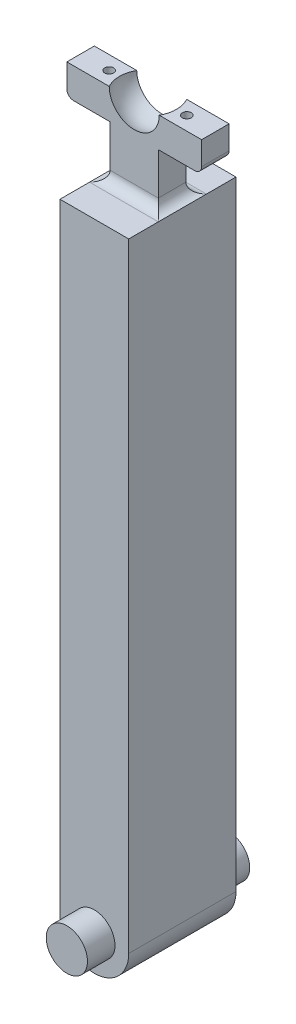
SolidWorks part; units mm, degrees
ref_plane "前视基准面" through (0, 0, 0) normal (0, 0, 1) x (1, 0, 0)
ref_plane "上视基准面" through (0, 0, 0) normal (0, 1, 0) x (1, 0, 0)
ref_plane "右视基准面" through (0, 0, 0) normal (1, 0, 0) x (0, 0, -1)
other "Configuration Table"
sketch "草图1" plane through (0, 0, 0) normal (0, 0, 1) x (1, 0, 0)
  line L0 (-5, 0) -> (5, 0)
  line L1 (5, 0) -> (5, 90)
  line L2 (5, 90) -> (-5, 90)
  line L3 (-5, 90) -> (-5, 0)
  line L7 (0, 0) -> (0, 22.7143) construction
  arc A0 (-5, 0) -> (5, 0) centre (0, 0) ccw
  dimension "D1" = 5
  dimension "D2" = 90
extrude "凸台-拉伸1" add sketch "草图1" along normal mid plane 15.6
sketch "草图4" plane through (0, 0, 7.8) normal (0, 0, 1) x (1, 0, 0)
  circle A0 centre (0, 0) radius 3
  dimension "D1" = 6
extrude "凸台-拉伸3" add sketch "草图4" along normal blind 4
ref_plane "基准面1" through (0, 102, 0) normal (0, 1, 0) x (1, 0, 0)
sketch "草图5" plane through (0, 102, 0) normal (0, 1, 0) x (1, 0, 0)
  line L1 (-3.5, 2) -> (3.5, 2)
  line L2 (-3.5, 2) -> (-3.5, -2)
  line L3 (-3.5, -2) -> (3.5, -2)
  line L4 (3.5, 2) -> (3.5, -2)
  line L5 (-3.5, 2) -> (3.5, -2) construction
  line L6 (-3.5, -2) -> (3.5, 2) construction
  point P0 (0, 0)
  dimension "D1" = 4
  dimension "D2" = 7
extrude "凸台-拉伸4" add sketch "草图5" against normal up to surface (12 mm away) up to face at (0, 90, 0)
sketch "草图7" plane through (0, 0, 0) normal (0, 0, 1) x (1, 0, 0)
  line L0 (0, 96.9511) -> (0, 94.9196) construction
  line L1 (-9.8, 102) -> (9.8, 102)
  line L2 (-9.8, 102) -> (-9.8, 97.6)
  line L3 (-9.8, 97.6) -> (9.8, 97.6)
  line L4 (9.8, 102) -> (9.8, 97.6)
  line L5 (-3.5, 102) -> (3.5, 102) construction
  dimension "D2" = 4.4
  dimension "D3" = 19.6
extrude "凸台-拉伸5" add sketch "草图7" along normal mid plane 4
sketch "草图8" plane through (0, 97.6, 0) normal (0, -1, 0) x (1, 0, 0)
  line L1 (-4.6108, -1.8) -> (-3.5715, 0)
  line L2 (-3.5715, 0) -> (-4.6108, 1.8)
  line L3 (-4.6108, 1.8) -> (-6.6892, 1.8)
  line L4 (-6.6892, 1.8) -> (-7.7285, 0)
  line L5 (-7.7285, 0) -> (-6.6892, -1.8)
  line L6 (-6.6892, -1.8) -> (-4.6108, -1.8)
  circle A0 centre (-5.65, 0) radius 1.8 construction
  dimension "D1" = 5.65
  dimension "D2" = 3.6
sketch "草图10" plane through (0, 0, 0) normal (0, 0, 1) x (1, 0, 0)
  line L0 (0, 106.15) -> (0, 97.85)
  line L1 (0, 102) -> (-4.15, 102)
  line L2 (-9.8, 102) -> (9.8, 102) construction
  circle A0 centre (0, 102) radius 4.15
  dimension "D2" = 8.3
  dimension "D1" = 90
revolve "切除-旋转1" cut sketch "草图10" angle 360 about L0
mirror "镜向2" about plane through (0, 0, 0) normal (0, 0, 1) of "凸台-拉伸3"
fillet "圆角2" radius 1 2 edges at (9.8, 97.6, 0) (-9.8, 97.6, 0)
hole_wizard "孔1" positions "草图11" profile "草图12" legacy end condition up to next
sketch "草图11" plane through (0, 97.6, 0) normal (0, -1, 0) x (-1, 0, 0)
  point P0 (5.65, 0)
  point P3 (-5.65, 0)
sketch "草图12" plane through (-5.65, 97.6, 0) normal (1, 0, 0) x (0, 0, -1)
  line L0 (0, 0) -> (0, 4.4)
  line L1 (0, 4.4) -> (0.65, 4.4)
  line L2 (0.65, 4.4) -> (0.65, 0)
  line L3 (0.65, 0) -> (0, 0)
  line L4 (0, 110) -> (0, -10) construction
  dimension "直径" = 1.3
  dimension "深度" = 4.4
fillet "圆角3" radius 1.5 4 edges at (3.5, 90, 0) (0, 90, 2) (-3.5, 90, 0) (0, 90, -2)
